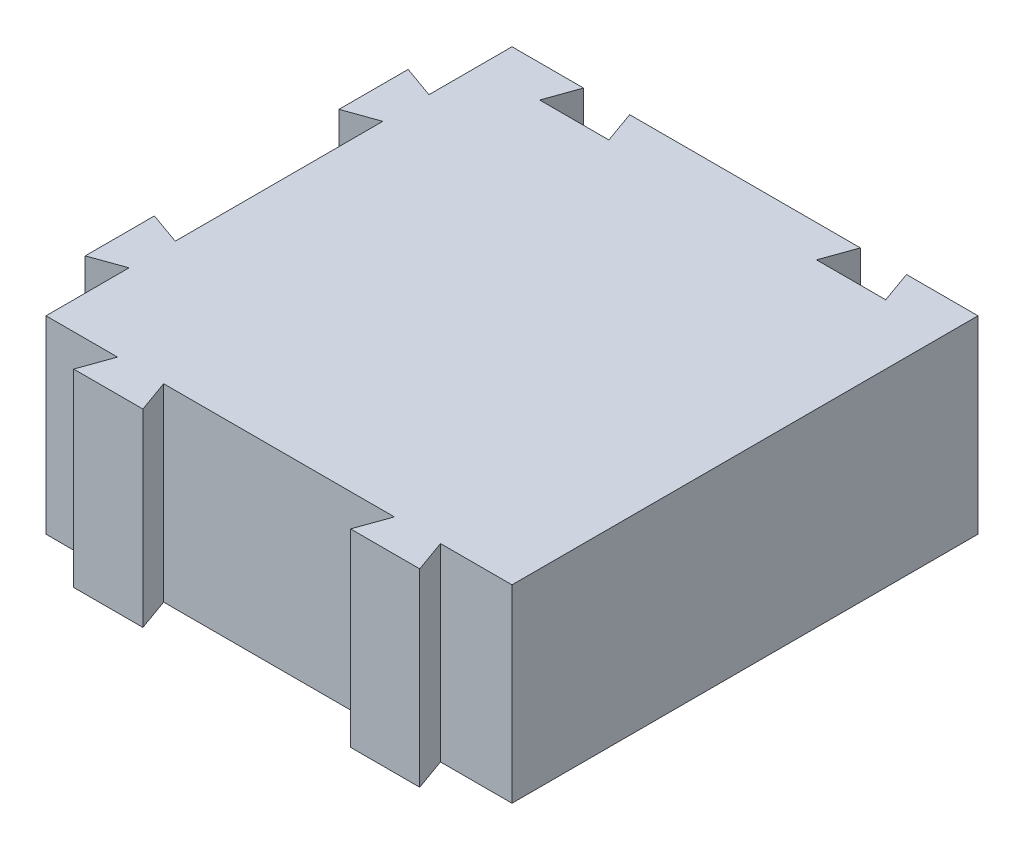
SolidWorks part; units mm, degrees
ref_plane "Front Plane" through (0, 0, 0) normal (0, 0, 1) x (1, 0, 0)
ref_plane "Top Plane" through (0, 0, 0) normal (0, 1, 0) x (1, 0, 0)
ref_plane "Right Plane" through (0, 0, 0) normal (1, 0, 0) x (0, 0, -1)
sketch "Sketch1" plane through (0, 0, 0) normal (0, 1, 0) x (1, 0, 0)
  line L0 (-14.0032, 0) -> (15.5031, 0) construction
  line L1 (-10.1, 10.1) -> (-7, 10.1)
  line L2 (-10.1, 10.1) -> (-10.1, 6.5)
  line L3 (-10.1, -10.1) -> (-7, -10.1)
  line L4 (10.1, 10.1) -> (10.1, 6.5)
  line L5 (0, 12.8597) -> (0, -11.7289) construction
  line L6 (-10.1, 6.5) -> (-11.5, 7)
  line L7 (-11.5, 7) -> (-11.5, 4)
  line L8 (-11.5, 4) -> (-10.1, 4.5)
  line L12 (-10.1, 4.5) -> (-10.1, -4.5)
  line L13 (10.1, 4.5) -> (10.1, -4.5)
  line L14 (7, 10.1) -> (7.5, 8.7)
  line L15 (7.5, 8.7) -> (4.5, 8.7)
  line L16 (4.5, 8.7) -> (5, 10.1)
  line L17 (7, 10.1) -> (10.1, 10.1)
  line L18 (-7, -10.1) -> (-7.5, -11.5)
  line L19 (-7.5, -11.5) -> (-4.5, -11.5)
  line L20 (-4.5, -11.5) -> (-5, -10.1)
  line L21 (-5, -10.1) -> (5, -10.1)
  line L22 (-11.5, -4) -> (-10.1, -4.5)
  line L23 (-11.5, -7) -> (-11.5, -4)
  line L24 (-10.1, -6.5) -> (-11.5, -7)
  line L25 (-10.1, -6.5) -> (-10.1, -10.1)
  line L26 (4.5, -11.5) -> (5, -10.1)
  line L27 (7.5, -11.5) -> (4.5, -11.5)
  line L28 (7, -10.1) -> (7.5, -11.5)
  line L29 (7, -10.1) -> (10.1, -10.1)
  line L30 (-4.5, 8.7) -> (-5, 10.1)
  line L31 (-7.5, 8.7) -> (-4.5, 8.7)
  line L32 (-7, 10.1) -> (-7.5, 8.7)
  line L33 (-5, 10.1) -> (5, 10.1)
  line L34 (10.1, -6.5) -> (10.1, -4.5)
  line L35 (10.1, 4.5) -> (10.1, 6.5)
  line L37 (10.1, -6.5) -> (10.1, -10.1)
  point P7 (-10.1, -10.1)
  point P10 (10.1, -10.1)
  point P13 (10.1, 10.1)
  dimension "D5" = 4.5
  dimension "D1" = 20.2
  dimension "D2" = 20.2
  dimension "D3" = 10.1
  dimension "D4" = 10.1
  dimension "D7" = 1.4
  dimension "D10" = 3
  dimension "D11" = 2
  dimension "D14" = 2
  dimension "D15" = 3
  dimension "D16" = 0.5
  dimension "D17" = 4.5
  dimension "D18" = 1.4
  dimension "D19" = 3
  dimension "D20" = 2
  dimension "D21" = 0.5
  dimension "D22" = 1.4
  dimension "D23" = 4.5
extrude "Boss-Extrude1" add sketch "Sketch1" along normal blind 8.2
